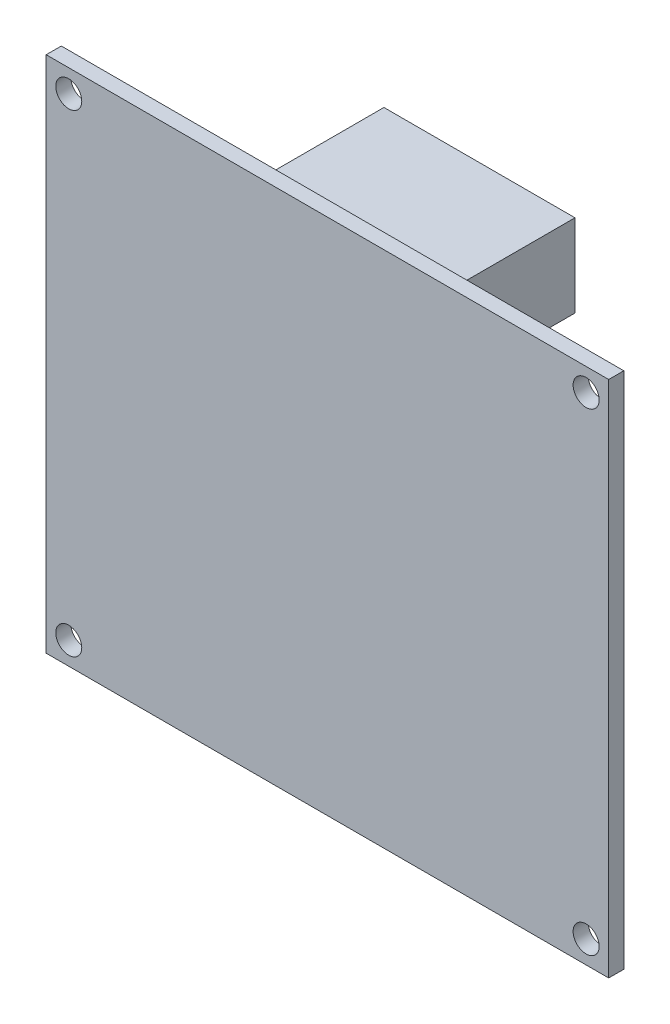
SolidWorks part; units mm, degrees
ref_plane "Front Plane" through (0, 0, 0) normal (0, 0, 1) x (1, 0, 0)
ref_plane "Top Plane" through (0, 0, 0) normal (0, 1, 0) x (1, 0, 0)
ref_plane "Right Plane" through (0, 0, 0) normal (1, 0, 0) x (0, 0, -1)
sketch "Sketch1" plane through (0, 0, 0) normal (0, 0, 1) x (1, 0, 0)
  line L0 (0, 0) -> (0, 40.1523) construction
  line L1 (-30.734, -28.321) -> (30.734, -28.321)
  line L2 (-30.734, -28.321) -> (-30.734, 28.321)
  line L3 (-30.734, 28.321) -> (30.734, 28.321)
  line L4 (30.734, -28.321) -> (30.734, 28.321)
  line L5 (-30.734, -28.321) -> (30.734, 28.321) construction
  line L6 (-30.734, 28.321) -> (30.734, -28.321) construction
  line L7 (0, 0) -> (61.2638, 0) construction
  point P0 (0, 0)
  dimension "D1" = 56.642
  dimension "D2" = 61.468
extrude "Boss-Extrude1" add sketch "Sketch1" along normal mid plane 1.651
sketch "Sketch3" plane through (0, 0, 0.8255) normal (0, 0, 1) x (1, 0, 0)
  line L0 (-30.734, 28.321) -> (-30.734, -28.321) construction
  line L1 (30.734, 28.321) -> (-30.734, 28.321) construction
  line L2 (0, 0) -> (43.9833, 0) construction
  line L3 (0, 0) -> (0, 30.5699) construction
  circle A0 centre (-28.2702, 25.8572) radius 1.4224
  circle A1 centre (28.2702, 25.8572) radius 1.4224
  circle A2 centre (28.2702, -25.8572) radius 1.4224
  circle A3 centre (-28.2702, -25.8572) radius 1.4224
  dimension "D1" = 2.8448
  dimension "D2" = 1.0414
  dimension "D3" = 1.0414
sketch "Sketch6" plane through (0, 0, -0.8255) normal (0, 0, -1) x (-1, 0, 0)
  line L1 (-30.734, 28.321) -> (30.734, 28.321) construction
  line L2 (-12.319, 18.034) -> (8.5598, 18.034)
  line L3 (-12.319, 18.034) -> (-12.319, 27.051)
  line L4 (-12.319, 27.051) -> (8.5598, 27.051)
  line L6 (8.5598, 18.034) -> (8.5598, 27.051)
  line L7 (30.734, 28.321) -> (30.734, -28.321) construction
  dimension "D1" = 1.27
  dimension "D2" = 22.1742
  dimension "D3" = 20.8788
  dimension "D4" = 9.017
extrude "Boss-Extrude3" add sketch "Sketch6" along normal blind 13.081
extrude "Cut-Extrude1" cut sketch "Sketch3" against normal through all
ref_axis "Axis1" through (-28.2702, 25.8572, -6.4824) along (0, 0, 1)
